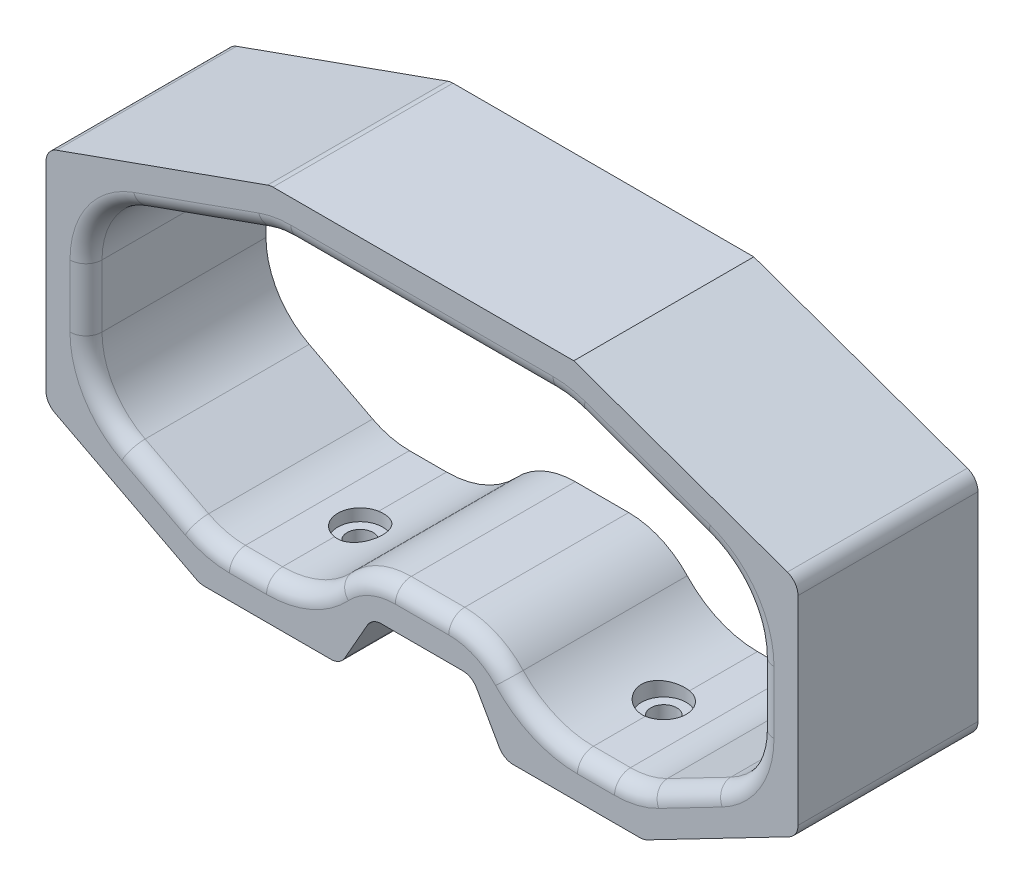
SolidWorks part; units mm, degrees
ref_plane "Front Plane" through (0, 0, 0) normal (0, 0, 1) x (1, 0, 0)
ref_plane "Top Plane" through (0, 0, 0) normal (0, 1, 0) x (1, 0, 0)
ref_plane "Right Plane" through (0, 0, 0) normal (1, 0, 0) x (0, 0, -1)
sketch "Base" plane through (0, 0, 0) normal (0, 0, 1) x (1, 0, 0)
  line L0 (0, 0) -> (7.0566, 0) construction
  line L1 (0, 14.8245) -> (0, 2.9308) construction
  line L2 (-27.725, 0) -> (-10.225, 0)
  line L3 (-10.225, 0) -> (-6.25, 7)
  line L4 (-6.25, 7) -> (6.25, 7)
  line L5 (-27.725, 0) -> (-47, 10)
  line L6 (-18.975, 9.727) -> (-18.975, 5.1122) construction
  line L7 (-47, 10) -> (-47, 37.5)
  line L8 (-47, 37.5) -> (-18.975, 47.5)
  line L9 (-18.975, 47.5) -> (18.975, 47.5)
  line L10 (18.975, 9.727) -> (18.975, 5.1122) construction
  line L11 (47, 37.5) -> (18.975, 47.5)
  line L12 (10.225, 0) -> (6.25, 7)
  line L13 (27.725, 0) -> (10.225, 0)
  line L14 (27.725, 0) -> (47, 10)
  line L15 (47, 10) -> (47, 37.5)
  line L16 (-41.4611, 23.75) -> (48.7296, 23.75) construction
  line L17 (0, 47.5) -> (0, 0) construction
  line L18 (-28.6707, 6.1235) -> (-36.6052, 10.24)
  line L19 (-42, 19.1165) -> (-42, 26.926)
  line L20 (-35.3607, 36.3444) -> (-19.7397, 41.9184)
  line L21 (-16.379, 42.5) -> (16.379, 42.5)
  line L22 (35.3607, 36.3444) -> (19.7397, 41.9184)
  line L23 (42, 19.1165) -> (42, 26.926)
  line L24 (28.6707, 6.1235) -> (36.6052, 10.24)
  line L25 (24.0655, 5) -> (13.1356, 5)
  line L26 (13.1356, 5) -> (12.0351, 6.938)
  line L27 (-3.3394, 12) -> (3.3394, 12)
  line L28 (-13.1356, 5) -> (-12.0351, 6.938)
  line L29 (-24.0655, 5) -> (-13.1356, 5)
  line L30 (42, 13.0388) -> (42, 33.9753) construction
  line L31 (26.5052, 5) -> (42, 13.0388) construction
  line L32 (42, 33.9753) -> (18.1097, 42.5) construction
  line L33 (-18.1097, 42.5) -> (18.1097, 42.5) construction
  line L34 (-42, 33.9753) -> (-18.1097, 42.5) construction
  line L35 (-42, 13.0388) -> (-42, 33.9753) construction
  line L36 (-26.5052, 5) -> (-42, 13.0388) construction
  line L37 (-26.5052, 5) -> (-13.1356, 5) construction
  line L38 (26.5052, 5) -> (13.1356, 5) construction
  line L39 (13.1356, 5) -> (9.1606, 12) construction
  line L40 (-9.1606, 12) -> (9.1606, 12) construction
  line L41 (-13.1356, 5) -> (-9.1606, 12) construction
  arc A0 (42, 19.1165) -> (36.6052, 10.24) centre (32, 19.1165) cw
  arc A1 (35.3607, 36.3444) -> (42, 26.926) centre (32, 26.926) cw
  arc A2 (16.379, 42.5) -> (19.7397, 41.9184) centre (16.379, 32.5) cw
  arc A3 (-19.7397, 41.9184) -> (-16.379, 42.5) centre (-16.379, 32.5) cw
  arc A4 (-42, 26.926) -> (-35.3607, 36.3444) centre (-32, 26.926) cw
  arc A5 (-36.6052, 10.24) -> (-42, 19.1165) centre (-32, 19.1165) cw
  arc A6 (-28.6707, 6.1235) -> (-24.0655, 5) centre (-24.0655, 15) ccw
  arc A7 (28.6707, 6.1235) -> (24.0655, 5) centre (24.0655, 15) cw
  arc A8 (12.0351, 6.938) -> (3.3394, 12) centre (3.3394, 2) ccw
  arc A9 (-3.3394, 12) -> (-12.0351, 6.938) centre (-3.3394, 2) ccw
  point P4 (-18.975, 0)
  point P7 (18.975, 0)
  point P20 (0, 47.5)
  point P22 (0, 7)
  point P27 (0, 23.75)
  dimension "D9" = 10
  dimension "D1" = 37.95
  dimension "D2" = 84
  dimension "D3" = 7
  dimension "D4" = 37.5
  dimension "D5" = 17.5
  dimension "D6" = 12.5
  dimension "D7" = 10
  dimension "D8" = 5
extrude "Boss-Extrude1" add sketch "Base" along normal blind 22.5
fillet "Fillet1" radius 12 2 edges at (13.1356, 5, 11.25) (-13.1356, 5, 11.25)
sketch "Screw_Mount" plane through (0, 0, 0) normal (0, 1, 0) x (1, 0, 0)
  line L0 (-18.975, 0) -> (-18.975, -35.419) construction
  line L1 (18.975, -39.4414) -> (18.975, -19.0631) construction
  line L2 (-25.4232, -22.5) -> (-8.2779, -22.5) construction
  line L4 (-27.725, -22.5) -> (-10.225, -22.5) construction
  line L5 (-26.591, 0) -> (-37.9378, 0) construction
  line L7 (-27.725, 0) -> (-10.225, 0) construction
  line L8 (0, 0) -> (0, -22.5) construction
  line L9 (0, -11.25) -> (-15.3122, -11.25) construction
  circle A0 centre (-18.975, -11.25) radius 2.8
  circle A1 centre (18.975, -11.25) radius 2.8
  circle A2 centre (-18.975, -11.25) radius 1.625
  circle A3 centre (18.975, -11.25) radius 1.625
  point P18 (0, -11.25)
  point P20 (-18.975, -11.25)
  point P22 (18.975, -11.25)
  dimension "D1" = 3.25
  dimension "D2" = 5.6
extrude "Cut-Extrude1" cut sketch "Screw_Mount" against normal blind 2 from offset 5.5 contours A2 | A0 A2 | A1 A3 | A3 region at (-21.6958, 0, 11.25) region at (16.2542, 0, 11.25) region at (-18.975, 0, 11.25) region at (18.975, 0, 11.25)
extrude "Cut-Extrude2" cut sketch "Screw_Mount<3>" against normal through all from surface contours A2 | A3 region at (-18.975, 0, 11.25) region at (18.975, 0, 11.25) starting at face at (-21.3674, 5, 11.25)
sketch "Screw_Mount<3>" plane through (0, 0, 0) normal (0, 1, 0) x (1, 0, 0) same geometry as "Screw_Mount"
fillet "Fillet3" radius 2 11 edges at (-27.725, 0, 11.25) (-47, 10, 11.25) (-47, 37.5, 11.25) (-18.975, 47.5, 11.25) (47, 37.5, 11.25) (47, 10, 11.25) (27.725, 0, 11.25) (-6.25, 7, 11.25) (6.25, 7, 11.25) (10.225, 0, 11.25) (-10.225, 0, 11.25)
fillet "Fillet4" radius 2 22 edges at (-7.328, 11.1701, 22.5) (0, 12, 22.5) (7.328, 11.1701, 22.5) (14.6465, 5.9959, 22.5) (21.7492, 5, 22.5) (26.4357, 5.2849, 22.5) (32.638, 8.1817, 22.5) (40.5455, 13.9228, 22.5) (42, 23.0212, 22.5) (40.1733, 32.6877, 22.5) (27.5502, 39.1314, 22.5) (18.0843, 42.3535, 22.5) (0, 42.5, 22.5) (-18.0843, 42.3535, 22.5) (-27.5502, 39.1314, 22.5) (-40.1733, 32.6877, 22.5) (-42, 23.0212, 22.5) (-40.5455, 13.9228, 22.5) (-32.638, 8.1817, 22.5) (-26.4357, 5.2849, 22.5) (-21.7492, 5, 22.5) (-14.6465, 5.9959, 22.5)
